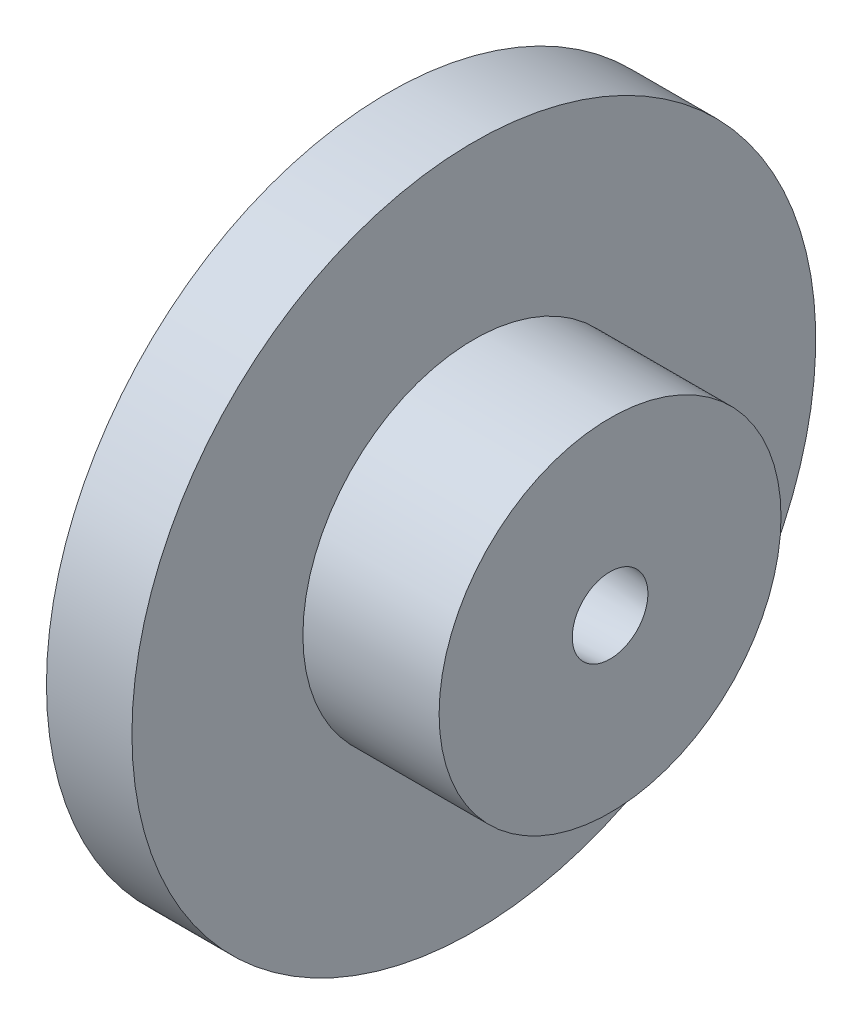
SolidWorks part; units mm, degrees
ref_plane "Front Plane" through (0, 0, 0) normal (0, 0, 1) x (1, 0, 0)
ref_plane "Top Plane" through (0, 0, 0) normal (0, 1, 0) x (1, 0, 0)
ref_plane "Right Plane" through (0, 0, 0) normal (1, 0, 0) x (0, 0, -1)
sketch "Sketch1" plane through (0, 0, 0) normal (0, 0, 1) x (1, 0, 0)
  line L0 (0, 0) -> (50000, 0) construction
  line L1 (0, 0) -> (0, 50000) construction
  line L2 (0, 8.5) -> (0, 50.8)
  line L3 (0, 50.8) -> (12.7, 50.8)
  line L4 (12.7, 50.8) -> (12.7, 25.4)
  line L5 (12.7, 25.4) -> (32.94, 25.4)
  line L6 (32.94, 25.4) -> (32.94, 5.6181)
  line L7 (32.94, 5.6181) -> (0, 8.5)
  dimension "D1" = 50.8
  dimension "D2" = 5
  dimension "D3" = 32.94
  dimension "D4" = 12.7
  dimension "D5" = 8.5
  dimension "D6" = 25.4
revolve "Revolve1" add sketch "Sketch1" angle 360 about L0
equation "\"d_major\"= 17mm"
equation "\"taper_angle\"= 5"
equation "\"d_workhold\"= 2"
equation "\"d_hub\"= 4"
equation "\"length\"= 32.94mm"
equation "\"l_hub\"= 0.5"
equation "\"D1@Sketch1\"=\"d_hub\"/2"
equation "\"D2@Sketch1\"=\"taper_angle\""
equation "\"D3@Sketch1\"=\"length\""
equation "\"D4@Sketch1\"=\"l_hub\""
equation "\"D5@Sketch1\"=\"d_major\"/2"
equation "\"D6@Sketch1\"=\"d_workhold\"/2"
